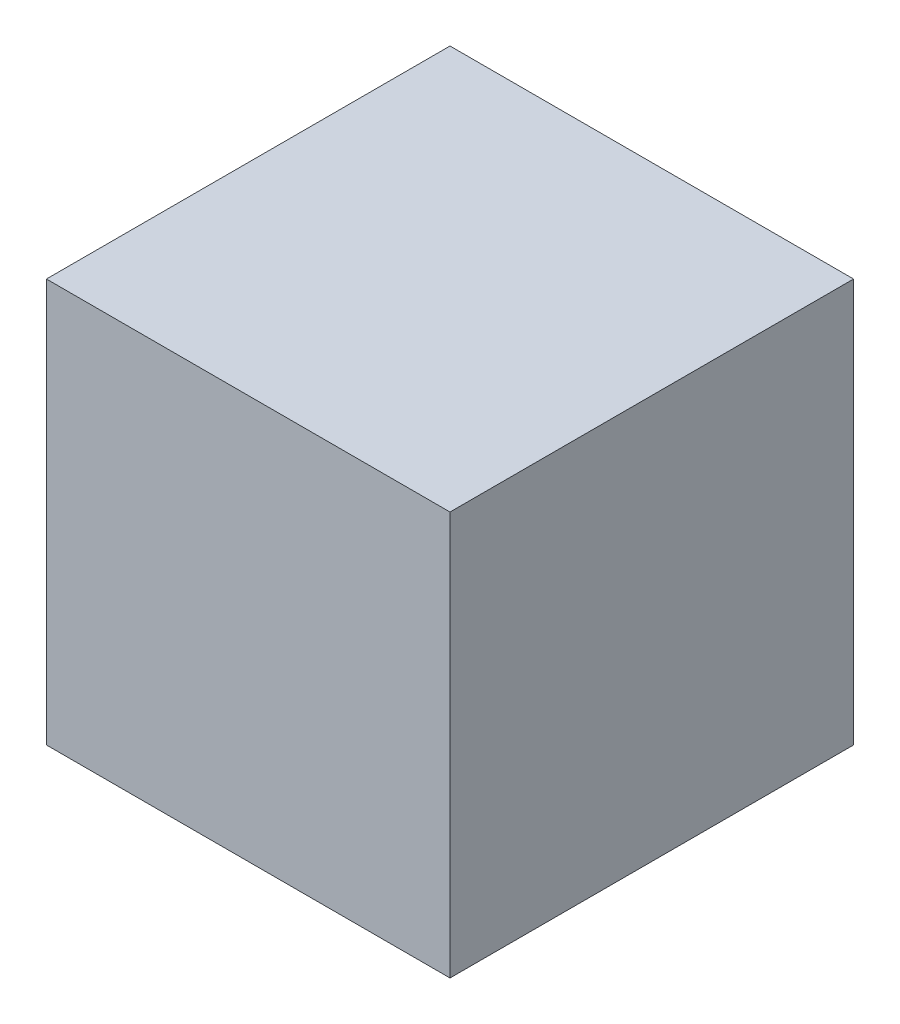
SolidWorks part; units mm, degrees
ref_plane "Front Plane" through (0, 0, 0) normal (0, 0, 1) x (1, 0, 0)
ref_plane "Top Plane" through (0, 0, 0) normal (0, 1, 0) x (1, 0, 0)
ref_plane "Right Plane" through (0, 0, 0) normal (1, 0, 0) x (0, 0, -1)
sketch "Sketch1" plane through (0, 0, 0) normal (0, 0, 1) x (1, 0, 0)
  line L1 (-127, -127) -> (127, -127)
  line L2 (-127, -127) -> (-127, 127)
  line L3 (-127, 127) -> (127, 127)
  line L4 (127, -127) -> (127, 127)
  line L5 (-127, -127) -> (127, 127) construction
  line L6 (-127, 127) -> (127, -127) construction
  point P0 (0, 0)
  dimension "D1" = 254
extrude "Boss-Extrude1" add sketch "Sketch1" along normal mid plane 254
equation "\"side_length\"= 10"
equation "\"D1@Sketch1\"=\"side_length\""
equation "\"D1@Boss-Extrude1\"=\"side_length\""
